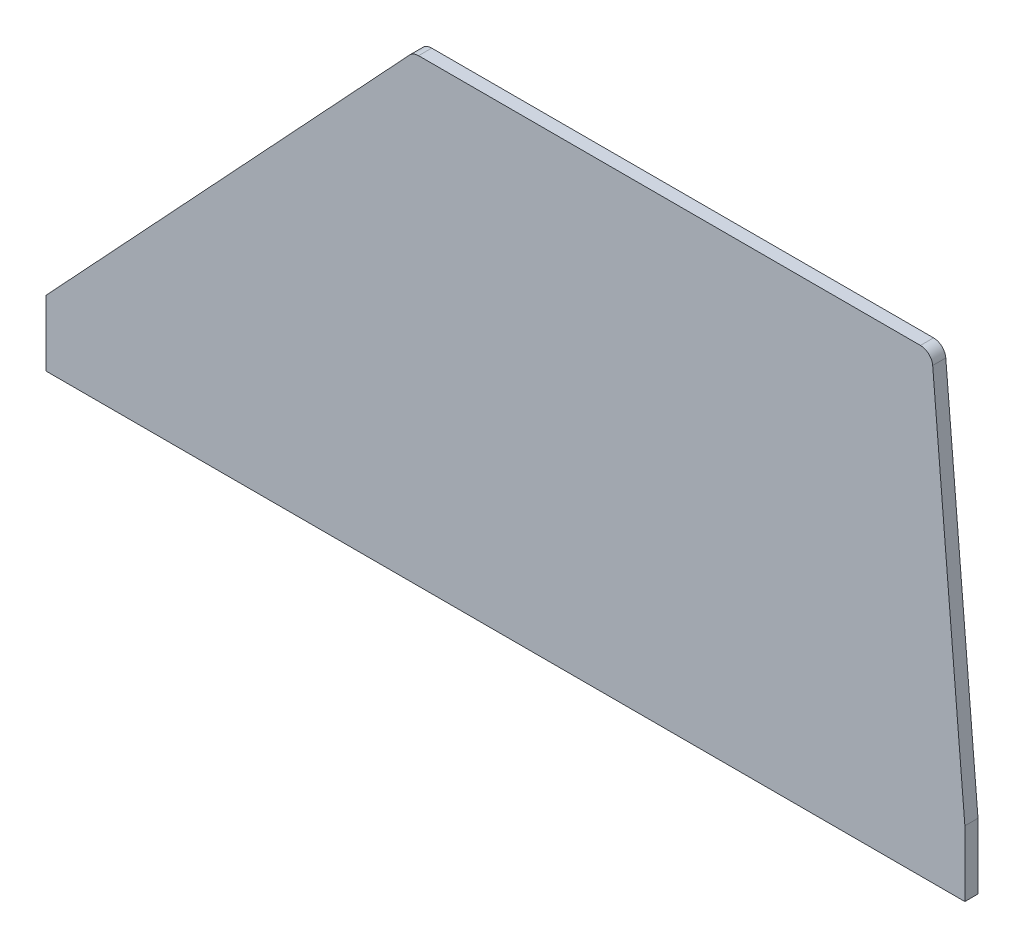
SolidWorks part; units mm, degrees
material "E-Glass Fiber"
ref_plane "Front Plane" through (0, 0, 0) normal (0, 0, 1) x (1, 0, 0)
ref_plane "Top Plane" through (0, 0, 0) normal (0, 1, 0) x (1, 0, 0)
ref_plane "Right Plane" through (0, 0, 0) normal (1, 0, 0) x (0, 0, -1)
sketch "Trapezoidal Fin Profile" plane through (0, 0, 0) normal (0, 0, 1) x (1, 0, 0)
  line L0 (381, -25.4) -> (0, -25.4)
  line L1 (0, -25.4) -> (0, 0)
  line L2 (0, 0) -> (156.7688, 152.4)
  line L3 (156.7688, 152.4) -> (359.9688, 152.4)
  line L5 (359.9688, 152.4) -> (381, 0)
  line L6 (381, 0) -> (381, -25.4)
  dimension "D2" = 381
  dimension "D3" = 203.2
  dimension "D4" = 156.7688
  dimension "D5" = 152.4
extrude "Trapezoidal Fin" [suppressed] add sketch "Trapezoidal Fin Profile" along normal blind 6.35 contours L2 L3 L5 L6 L0 L1
fillet "Trapezoidal Fin Fillets" [suppressed] radius 4.7625
sketch "Swept Fin Profile" [suppressed] plane through (0, 0, 0) normal (0, 0, 1) x (1, 0, 0)
  line L0 (0, 0) -> (267.9954, 0)
  line L1 (267.9954, 0) -> (398.268, 159.4104)
  line L2 (398.268, 159.4104) -> (264.2576, 159.4104)
  line L3 (264.2576, 159.4104) -> (0, 0)
  line L5 (52.0954, 0) -> (242.5954, 0)
  line L6 (52.0954, 0) -> (52.0954, -25.4)
  line L7 (52.0954, -25.4) -> (242.5954, -25.4)
  line L8 (242.5954, 0) -> (242.5954, -25.4)
  dimension "D1" = 267.9954
  dimension "D2" = 159.4104
  dimension "D3" = 134.0104
  dimension "D4" = 31.1
  dimension "D6" = 25.4
  dimension "D7" = 190.5
extrude "Boss-Extrude2" [suppressed] add sketch "Swept Fin Profile" along normal blind 6.35 contours L8 L0 L6 L7 | L0 L1 L2 L3
fillet "Fillet1" [suppressed] radius 4.7625
sketch "Sketch1" plane through (0, 0, 0) normal (0, 0, 1) x (1, 0, 0)
  line L0 (0, 0) -> (142.113, 152.3975)
  line L1 (142.113, 152.3975) -> (342.773, 152.3975)
  line L2 (342.773, 152.3975) -> (355.6, -0.0025)
  line L3 (355.6, -0.0025) -> (355.6, -25.4)
  line L4 (355.6, -25.4) -> (0, -25.4)
  line L5 (0, -25.4) -> (0, 0)
  dimension "D1" = 355.6
  dimension "D2" = 200.66
  dimension "D3" = 25.4
  dimension "D4" = 142.113
  dimension "D5" = 43
  dimension "D6" = 152.4
extrude "Boss-Extrude3" add sketch "Sketch1" along normal mid plane 5.08
fillet "Fillet2" radius 4.7625 2 edges at (342.773, 152.3975, 0) (142.113, 152.3975, 0)
equation "\"Root Chord\"= 15"
equation "\"Span\"= 6"
equation "\"Tip Chord\"= 8"
equation "\"Sweep Distance\"= 6.1720"
equation "\"Fin Thickness\"= 0.25"
equation "\"Tab Height\"= 1"
equation "\"D1@Trapezoidal Fin Profile\" = \"Tab Height\""
equation "\"D2@Trapezoidal Fin Profile\" = \"Root Chord\""
equation "\"D3@Trapezoidal Fin Profile\" = \"Tip Chord\""
equation "\"D4@Trapezoidal Fin Profile\" = \"Sweep Distance\""
equation "\"D5@Trapezoidal Fin Profile\" = \"Span\""
equation "\"Fillet Radius\"=0.1875"
equation "\"D1@Trapezoidal Fin Fillets\"=\"Fillet Radius\""
equation "\"D1@Swept Fin Profile\" = 10.551"
equation "\"D4@Swept Fin Profile\" = 90 - 58.9"
